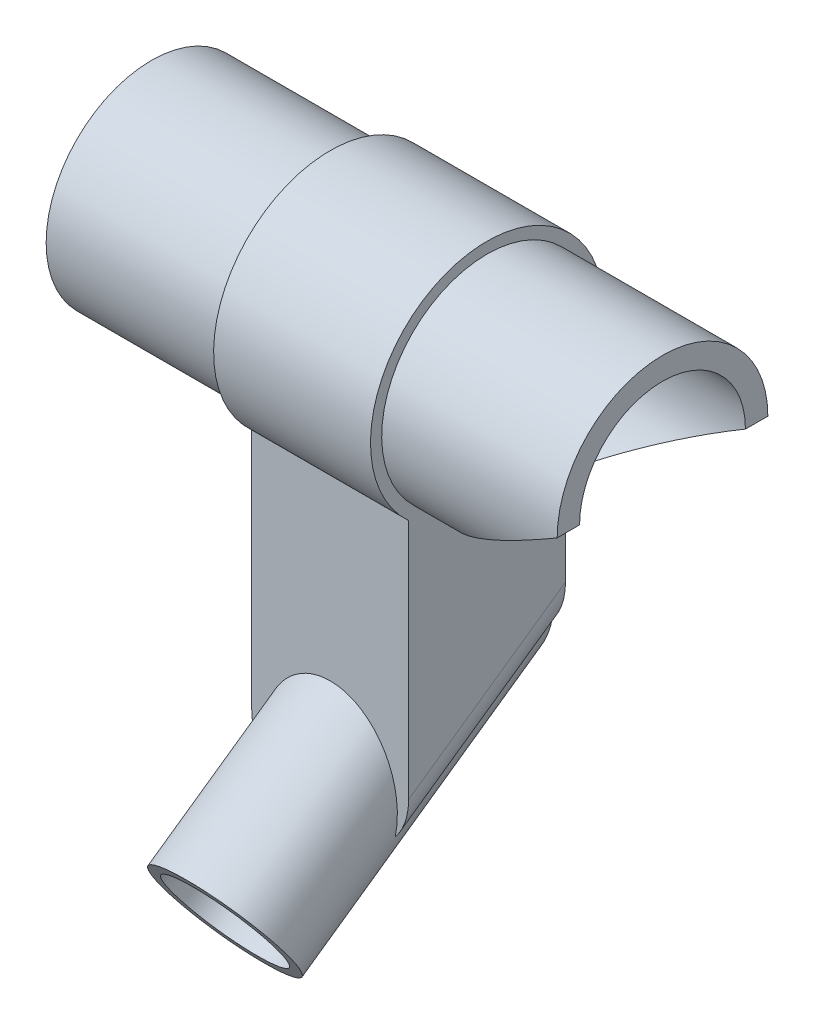
SolidWorks part; units mm, degrees
ref_plane "Alzado" through (0, 0, 0) normal (0, 0, 1) x (1, 0, 0)
ref_plane "Planta" through (0, 0, 0) normal (0, 1, 0) x (1, 0, 0)
ref_plane "Vista lateral" through (0, 0, 0) normal (1, 0, 0) x (0, 0, -1)
sketch "Croquis1" plane through (0, 0, 0) normal (1, 0, 0) x (0, 0, -1)
  circle A0 centre (0, 0) radius 18.5
  circle A1 centre (0, 0) radius 23.5
  dimension "D1" = 37
  dimension "D2" = 5
extrude "Saliente-Extruir1" add sketch "Croquis1" along normal blind 114
sketch "Croquis2" plane through (0, 0, 0) normal (-1, 0, 0) x (0, 0, 1)
  circle A0 centre (0, 0) radius 5.375
  circle A1 centre (0, 0) radius 23.5
  circle A2 centre (-12.4762, 6.3517) radius 1.25
  circle A3 centre (-6.3517, -12.4762) radius 1.25
  circle A4 centre (12.4762, -6.3517) radius 1.25
  circle A5 centre (6.3517, 12.4762) radius 1.25
  dimension "D1" = 2.5
  dimension "D2" = 47
extrude "Saliente-Extruir2" add sketch "Croquis2" against normal blind 5
sketch "Croquis4" plane through (0, 0, 0) normal (0, 0, 1) x (1, 0, 0)
  line L0 (114, 0) -> (74, -23.5)
  line L1 (0, -23.5) -> (114, -23.5) construction
  line L2 (74, -23.5) -> (114, -23.5)
  line L3 (114, -23.5) -> (114, 0)
  dimension "D1" = 23.5
  dimension "D2" = 40
extrude "Cortar-Extruir1" cut sketch "Croquis4" against normal mid plane 47
sketch "Croquis6" plane through (5, 0, 0) normal (1, 0, 0) x (0, 0, -1)
  circle A0 centre (0, 0) radius 11.5
  dimension "D1" = 23
extrude "Cortar-Extruir2" cut sketch "Croquis6" against normal blind 2.5
sketch "Croquis17" plane through (0, 0, 0) normal (0, 1, 0) x (1, 0, 0)
  line L1 (39.8579, 17.5) -> (74.8579, 17.5)
  line L2 (39.8579, 17.5) -> (39.8579, -17.5)
  line L3 (39.8579, -17.5) -> (74.8579, -17.5)
  line L4 (74.8579, 17.5) -> (74.8579, -17.5)
  line L5 (39.8579, 17.5) -> (74.8579, -17.5) construction
  line L6 (39.8579, -17.5) -> (74.8579, 17.5) construction
  dimension "D1" = 35
extrude "Saliente-Extruir3" add sketch "Croquis17" against normal blind 65
sketch3d "Croquis3D4"
  line L0 (57.3579, -65, 0) -> (57.3579, -93.6788, -40.9576) construction
  line L1 (57.3579, -93.6788, -40.9576) -> (57.3579, -93.6788, 40.9576) construction
  line L2 (57.3579, -65, 0) -> (57.3579, -65, -44.525) construction
  line L3 (74.8579, -65, -17.5) -> (39.8579, -65, 17.5) construction
  line L4 (57.3579, -65, 0) -> (65.365, -65, 0) construction
  line L5 (57.3579, -93.6788, 40.9576) -> (57.3579, -65, 0) construction
  point P2 (57.3579, -65, 0)
  dimension "D1" = 35
  dimension "D2" = 50
  dimension "D3" = 90
ref_plane "Plano4" through (57.3579, -93.6788, 40.9576) normal (0, 0.5736, -0.8192) x (-1, 0, 0)
sketch "Croquis18" plane through (57.3579, -93.6788, 40.9576) normal (0, 0.5736, -0.8192) x (-1, 0, 0)
  circle A0 centre (0, 0) radius 15
  circle A1 centre (0, 0) radius 12.5
  dimension "D1" = 25
  dimension "D2" = 30
extrude "Saliente-Extruir4" add sketch "Croquis18" along normal blind 70
ref_plane "Plano5" through (57.3579, 0, 0) normal (1, 0, 0) x (0, 0, -1)
sketch "Croquis26" plane through (0, -65, 0) normal (0, -1, 0) x (1, 0, 0)
  line L0 (39.8579, 17.5) -> (74.8579, 17.5)
  line L1 (74.8579, 17.5) -> (74.8579, -17.5)
  line L2 (74.8579, -17.5) -> (39.8579, -17.5)
  line L3 (39.8579, -17.5) -> (39.8579, 17.5)
extrude "Saliente-Extruir8" add sketch "Croquis26" along normal blind 40
sketch "Croquis23" plane through (0, -50.0632, 71.4976) normal (0, -0.5736, 0.8192) x (-1, -0.0003, -0.0002)
  line L0 (-72.3387, 53.2656) -> (-106.2851, 53.2656)
  line L1 (-42.3387, 53.2656) -> (-8.3922, 53.2656)
  arc A3 (-8.3922, 53.2656) -> (-106.2851, 53.2656) centre (-57.3387, 53.2656) ccw
  arc A4 (-42.3387, 53.2656) -> (-72.3387, 53.2656) centre (-57.3387, 53.2656) ccw
extrude "Cortar-Extruir4" cut sketch "Croquis23" against normal through all
sketch "Croquis25" plane through (39.8579, 0, 0) normal (-1, 0, 0) x (0, 0, 1)
  line L0 (-17.5, -38.7992) -> (-17.5, -83.2732)
  line L2 (-17.5, -83.2732) -> (-30.8368, -83.2732)
  line L3 (-30.8368, -83.2732) -> (-30.8368, -38.7992)
  line L4 (-30.8368, -38.7992) -> (-17.5, -38.7992)
  line L5 (-17.5, -52.7541) -> (-17.5, -15.6844) construction
chamfer "Chaflán1" distance 5 angle 45 2 edges at (72.3579, -64.9934, 0) (42.3579, -65.0066, 0)
fillet "Redondeo1" radius 10 2 edges at (74.8579, -66.7563, 0) (39.8579, -66.7707, 0)
sketch "Croquis27" plane through (39.8579, 0, 0) normal (-1, 0, 0) x (0, 0, 1)
  circle A0 centre (0, 0) radius 26
  dimension "D1" = 52
extrude "Saliente-Extruir9" add sketch "Croquis27" against normal blind 35
sketch "Croquis28" plane through (74.8579, 0, 0) normal (1, 0, 0) x (0, 0, -1)
  circle A0 centre (0, 0) radius 18.5
extrude "Cortar-Extruir7" cut sketch "Croquis28" against normal blind 35
extrude "Cortar-Extruir8" cut sketch "Croquis25" against normal blind 35
